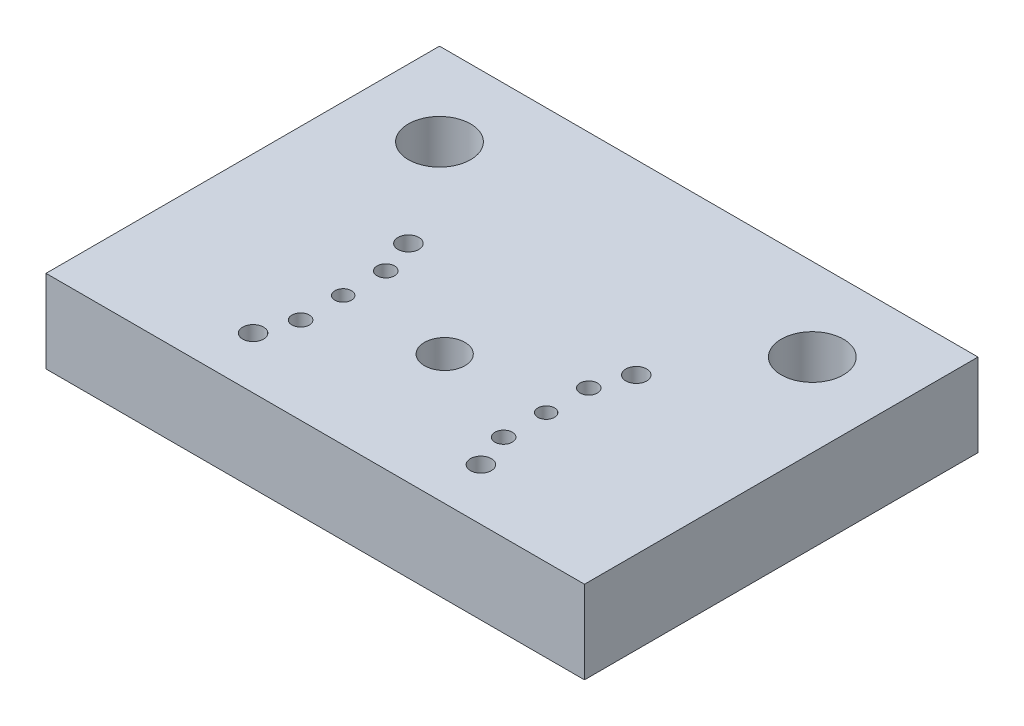
SolidWorks part; units mm, degrees
material "Plain Carbon Steel"
ref_plane "Front Plane" through (0, 0, 0) normal (0, 0, 1) x (1, 0, 0)
ref_plane "Top Plane" through (0, 0, 0) normal (0, 1, 0) x (1, 0, 0)
ref_plane "Right Plane" through (0, 0, 0) normal (1, 0, 0) x (0, 0, -1)
sketch "Sketch1" plane through (0, 0, 0) normal (0, 1, 0) x (1, 0, 0)
  line L0 (-130, 30) -> (130, 30) construction
  line L1 (-130, -95) -> (130, -95)
  line L2 (-130, -95) -> (-130, 95)
  line L3 (-130, 95) -> (130, 95)
  line L4 (130, -95) -> (130, 95)
  line L5 (-130, -95) -> (130, 95) construction
  line L6 (-130, 95) -> (130, -95) construction
  point P0 (0, 0)
  dimension "D1" = 260
  dimension "D2" = 190
  dimension "D3" = 125
extrude "Boss-Extrude1" add sketch "Sketch1" against normal blind 40
sketch "Sketch2" plane through (0, 0, 0) normal (0, 1, 0) x (1, 0, 0)
  line L0 (0, -95) -> (0, 95) construction
  line L1 (-130, -95) -> (130, -95) construction
  line L2 (130, 95) -> (-130, 95) construction
  circle A0 centre (-90, 55) radius 15
  circle A1 centre (90, 55) radius 15
  dimension "D2" = 30
  dimension "D1" = 180
  dimension "D3" = 150
extrude "Cut-Extrude1" cut sketch "Sketch2" against normal through all
ref_plane "Centre" through (0, 0, 32.5) normal (0, 0, 1) x (1, 0, 0)
sketch "Sketch3" plane through (0, -40, 0) normal (0, -1, 0) x (1, 0, 0)
  circle A0 centre (-55, 70) radius 5.05
  circle A1 centre (55, 70) radius 5.05
  circle A2 centre (55, -5) radius 5.05
  circle A3 centre (-55, -5) radius 5.05
  dimension "D1" = 10.1
extrude "Cut-Extrude2" cut sketch "Sketch3" against normal through all
sketch "Sketch4" plane through (0, -40, 0) normal (0, -1, 0) x (1, 0, 0)
  circle A2 centre (0, 32.5) radius 9.7705
  circle A3 centre (0, 32.5) radius 9.7705
  dimension "D1" = 3.2
extrude "Cut-Extrude3" cut sketch "Sketch4" against normal through all
hole_wizard "CBORE for M8 Hex Socket Head Cap Screw1" positions "Sketch11" profile "Sketch6" counterbore size "M8" standard "ISO" end condition through all
sketch "Sketch11" plane through (0, -40, 0) normal (0, -1, 0) x (-1, 0, 0)
  point P0 (-49, -11.95)
  point P3 (-49, -53.05)
  point P6 (49, -53.05)
  point P9 (49, -11.95)
sketch "Sketch6" plane through (49, -40, 11.95) normal (1, 0, 0) x (0, 0, -1)
  line L0 (0, 0) -> (0, 40)
  line L1 (0, 40) -> (4.2, 40)
  line L3 (4.2, 40) -> (4.2, 8.6)
  line L4 (4.2, 8.6) -> (7.5, 8.6)
  line L5 (7.5, 8.6) -> (7.5, 0)
  line L7 (7.5, 0) -> (0, 0)
  line L11 (0, -6.35) -> (0, 107.95) construction
  dimension "Thru Hole Dia." = 8.4
  dimension "Thru Hole Depth" = 40
  dimension "C'Bore Dia." = 15
  dimension "C'Bore Depth" = 8.6
hole_wizard "Ø8.0mm Dowel Hole1" positions "Sketch10" profile "Sketch9" hole size "Ø8.0" standard "ISO" end condition through all
sketch "Sketch10" plane through (0, -40, 0) normal (0, -1, 0) x (-1, 0, 0)
  point P0 (-49, -32.5)
  point P3 (49, -32.5)
sketch "Sketch9" plane through (49, -40, 32.5) normal (1, 0, 0) x (0, 0, -1)
  line L0 (0, 0) -> (0, 40)
  line L1 (0, 40) -> (4, 40)
  line L2 (4, 40) -> (4, 0)
  line L5 (4, 0) -> (0, 0)
  line L11 (0, -6.35) -> (0, 107.95) construction
  dimension "Thru Hole Dia." = 8
  dimension "Thru Hole Depth" = 40
